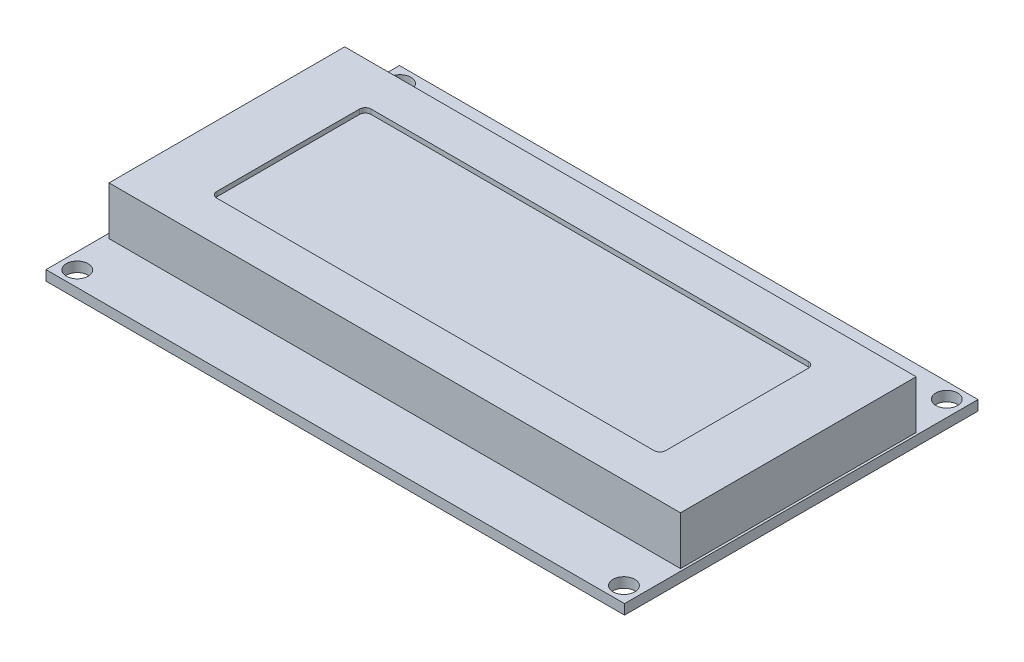
SolidWorks part; units mm, degrees
ref_plane "前基準面" through (0, 0, 0) normal (0, 0, 1) x (1, 0, 0)
ref_plane "上基準面" through (0, 0, 0) normal (0, 1, 0) x (1, 0, 0)
ref_plane "右基準面" through (0, 0, 0) normal (1, 0, 0) x (0, 0, -1)
sketch "草圖1" plane through (0, 0, 0) normal (0, 1, 0) x (1, 0, 0)
  line L0 (0, 0) -> (49.1, 0) construction
  line L1 (-49.1, -30) -> (49.1, -30)
  line L2 (-49.1, -30) -> (-49.1, 30)
  line L3 (-49.1, 30) -> (49.1, 30)
  line L4 (49.1, -30) -> (49.1, 30)
  line L5 (-49.1, -30) -> (49.1, 30) construction
  line L6 (-49.1, 30) -> (49.1, -30) construction
  line L7 (0, 0) -> (0, 30) construction
  circle A0 centre (46.4, 27.4) radius 1.85
  circle A1 centre (-46.4, 27.4) radius 1.85
  circle A2 centre (46.4, -27.4) radius 1.85
  circle A3 centre (-46.4, -27.4) radius 1.85
  point P0 (0, 0)
  point P13 (0, 0)
  dimension "D3" = 3.7
  dimension "D1" = 60
  dimension "D2" = 98.2
  dimension "D4" = 92.8
  dimension "D5" = 54.8
extrude "填料-伸長1" add sketch "草圖1" along normal blind 1.7
sketch "草圖2" plane through (0, 0, 0) normal (0, 1, 0) x (1, 0, 0)
  line L0 (49.1, 30) -> (-49.1, 30) construction
  line L1 (-48.3, 19.9) -> (48.7, 19.9)
  line L2 (-48.3, 19.9) -> (-48.3, -20.1)
  line L3 (-48.3, -20.1) -> (48.7, -20.1)
  line L4 (48.7, 19.9) -> (48.7, -20.1)
  line L5 (-49.1, 30) -> (-49.1, -30) construction
  dimension "D1" = 97
  dimension "D2" = 40
  dimension "D3" = 10.1
  dimension "D4" = 0.8
extrude "填料-伸長2" add sketch "草圖2" along normal blind 9.9
sketch "草圖3" plane through (0, 9.9, 0) normal (0, 1, 0) x (1, 0, 0)
  line L0 (-48.3, 19.9) -> (48.7, -20.1) construction
  line L5 (48.7, 19.9) -> (-48.3, -20.1) construction
  line L7 (-36.9, -13.2) -> (37.3, -13.2)
  line L8 (-37.9, -12.2) -> (-37.9, 12)
  line L9 (-36.9, 13) -> (37.3, 13)
  line L10 (38.3, -12.2) -> (38.3, 12)
  line L11 (-37.9, -13.2) -> (38.3, 13) construction
  line L12 (-37.9, 13) -> (38.3, -13.2) construction
  arc A0 (-36.9, -13.2) -> (-37.9, -12.2) centre (-36.9, -12.2) cw
  arc A1 (37.3, -13.2) -> (38.3, -12.2) centre (37.3, -12.2) ccw
  arc A2 (38.3, 12) -> (37.3, 13) centre (37.3, 12) ccw
  arc A3 (-36.9, 13) -> (-37.9, 12) centre (-36.9, 12) ccw
  point P0 (0.2, -0.1)
  dimension "D3" = 1
  dimension "D1" = 76.2
  dimension "D2" = 26.2
extrude "除料-伸長1" cut sketch "草圖3" against normal blind 0.8
sketch "草圖4" plane through (0, 0, 0) normal (0, 1, 0) x (1, 0, 0)
  line L0 (49.1, 30) -> (-49.1, 30) construction
  line L1 (0.7, 28.9) -> (-41.3, 28.9)
  line L2 (0.7, 28.9) -> (0.7, 9.3)
  line L3 (0.7, 9.3) -> (-41.3, 9.3)
  line L4 (-41.3, 28.9) -> (-41.3, 9.3)
  line L5 (-49.1, 30) -> (-49.1, -30) construction
  dimension "D1" = 42
  dimension "D2" = 19.6
  dimension "D3" = 1.1
  dimension "D4" = 7.8
extrude "填料-伸長3" add sketch "草圖4" against normal blind 1.5 from offset 2.7 separate body offset against normal yes
sketch "草圖5" plane through (0, 0, 0) normal (0, 1, 0) x (1, 0, 0)
  line L0 (-41.3, 28.9) -> (-41.3, 9.3) construction
  line L1 (-40.3, 26.3) -> (0.4, 26.3)
  line L2 (-40.3, 26.3) -> (-40.3, 28.9)
  line L3 (-40.3, 28.9) -> (0.4, 28.9)
  line L4 (0.4, 26.3) -> (0.4, 28.9)
  line L5 (0.7, 28.9) -> (-41.3, 28.9) construction
  point P6 (-40.3, 28.9)
  dimension "D1" = 2.6
  dimension "D2" = 40.7
  dimension "D3" = 1
extrude "填料-伸長4" add sketch "草圖5" against normal up to surface (2.7 mm away) up to face at (-20.3, -2.7, -19.1)
sketch "草圖6" plane through (0, -4.2, 0) normal (0, -1, 0) x (1, 0, 0)
  line L0 (0.7, -28.9) -> (-41.3, -28.9) construction
  line L1 (-33.5, -17.7) -> (-26.5, -17.7)
  line L2 (-33.5, -17.7) -> (-33.5, -24.7)
  line L3 (-33.5, -24.7) -> (-26.5, -24.7)
  line L4 (-26.5, -17.7) -> (-26.5, -24.7)
  line L5 (-33.5, -17.7) -> (-26.5, -24.7) construction
  line L6 (-33.5, -24.7) -> (-26.5, -17.7) construction
  line L7 (-22.9, -15.2) -> (-15.4, -15.2)
  line L8 (-22.9, -15.2) -> (-22.9, -25.7)
  line L9 (-22.9, -25.7) -> (-15.4, -25.7)
  line L10 (-15.4, -15.2) -> (-15.4, -25.7)
  line L11 (-22.9, -15.2) -> (-15.4, -25.7) construction
  line L12 (-22.9, -25.7) -> (-15.4, -15.2) construction
  line L13 (-41.3, -28.9) -> (-41.3, -9.3) construction
  point P0 (-30, -21.2)
  point P5 (-19.15, -20.45)
  point P10 (-20.9132, -19.3582)
  dimension "D1" = 7
  dimension "D2" = 7
  dimension "D3" = 4.2
  dimension "D4" = 7.8
  dimension "D5" = 10.5
  dimension "D6" = 7.5
  dimension "D7" = 3.2
  dimension "D8" = 25.9
extrude "填料-伸長5" add sketch "草圖6" along normal blind 5 contours L4 L1 L2 L3 region at (-30, -4.2, -21.2)
extrude "填料-伸長6" add sketch "草圖6<3>" along normal blind 2.2 contours L10 L7 L8 L9 region at (-19.15, -4.2, -20.45)
sketch "草圖6<3>" plane through (0, -4.2, 0) normal (0, -1, 0) x (1, 0, 0) same geometry as "草圖6"
